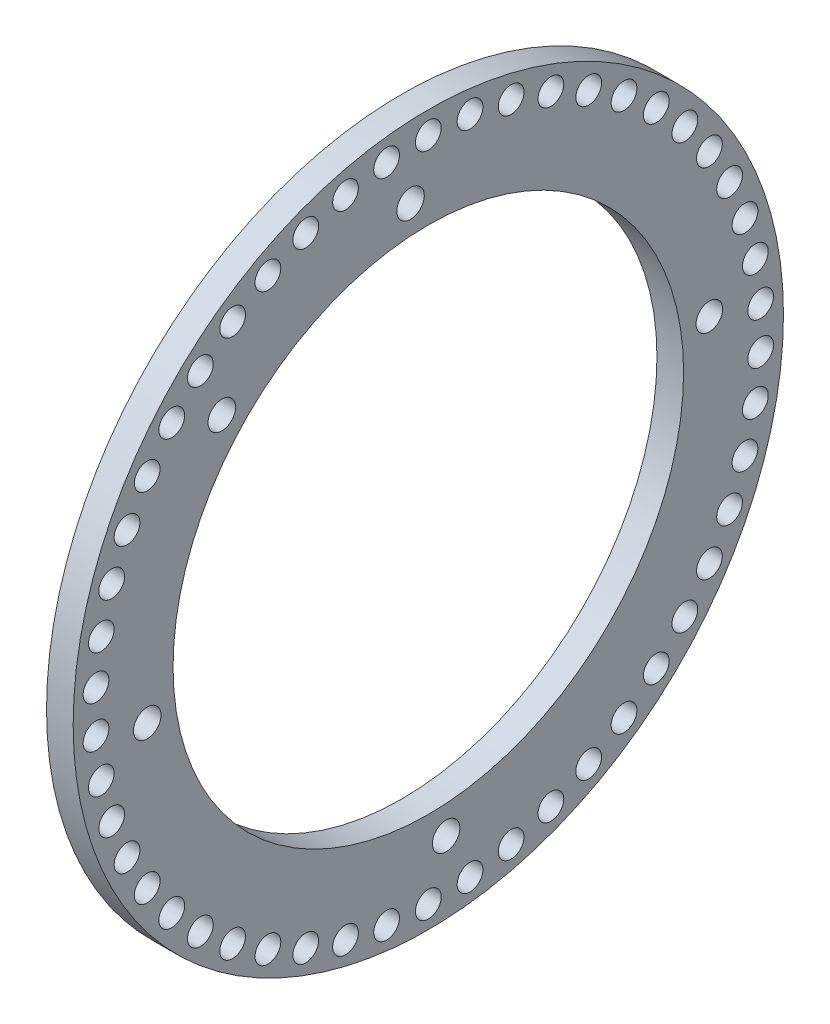
SolidWorks part; units mm, degrees
material "AISI 304"
ref_plane "Front Plane" through (0, 0, 0) normal (0, 0, 1) x (1, 0, 0)
ref_plane "Top Plane" through (0, 0, 0) normal (0, 1, 0) x (1, 0, 0)
ref_plane "Right Plane" through (0, 0, 0) normal (1, 0, 0) x (0, 0, -1)
sketch "Sketch1" plane through (0, 0, 0) normal (1, 0, 0) x (0, 0, -1)
  line L0 (0, 0) -> (0, 40) construction
  line L66 (0, 0) -> (40, 0) construction
  line L67 (0, 0) -> (-40, 0) construction
  line L72 (0, 0) -> (0, -40) construction
  circle A3 centre (0, 0) radius 40
  circle A24 centre (0, 37.5) radius 1.45
  circle A25 centre (0, 0) radius 28.75
  circle A26 centre (4.7, 37.2043) radius 1.45
  circle A27 centre (9.3259, 36.3219) radius 1.45
  circle A28 centre (13.8047, 34.8666) radius 1.45
  circle A29 centre (18.0658, 32.8615) radius 1.45
  circle A30 centre (22.0419, 30.3381) radius 1.45
  circle A31 centre (25.6705, 27.3363) radius 1.45
  circle A32 centre (28.8942, 23.9034) radius 1.45
  circle A33 centre (31.6623, 20.0935) radius 1.45
  circle A34 centre (33.931, 15.9667) radius 1.45
  circle A35 centre (35.6646, 11.5881) radius 1.45
  circle A36 centre (36.8358, 7.0268) radius 1.45
  circle A37 centre (37.426, 2.3546) radius 1.45
  circle A38 centre (37.426, -2.3546) radius 1.45
  circle A39 centre (36.8358, -7.0268) radius 1.45
  circle A40 centre (35.6646, -11.5881) radius 1.45
  circle A41 centre (33.931, -15.9667) radius 1.45
  circle A42 centre (31.6623, -20.0935) radius 1.45
  circle A43 centre (28.8942, -23.9034) radius 1.45
  circle A44 centre (25.6705, -27.3363) radius 1.45
  circle A45 centre (22.0419, -30.3381) radius 1.45
  circle A46 centre (18.0658, -32.8615) radius 1.45
  circle A47 centre (13.8047, -34.8666) radius 1.45
  circle A48 centre (9.3259, -36.3219) radius 1.45
  circle A49 centre (4.7, -37.2043) radius 1.45
  circle A50 centre (0, -37.5) radius 1.45
  circle A51 centre (-4.7, -37.2043) radius 1.45
  circle A52 centre (-9.3259, -36.3219) radius 1.45
  circle A53 centre (-13.8047, -34.8666) radius 1.45
  circle A54 centre (-18.0658, -32.8615) radius 1.45
  circle A55 centre (-22.0419, -30.3381) radius 1.45
  circle A56 centre (-25.6705, -27.3363) radius 1.45
  circle A57 centre (-28.8942, -23.9034) radius 1.45
  circle A58 centre (-31.6623, -20.0935) radius 1.45
  circle A59 centre (-33.931, -15.9667) radius 1.45
  circle A60 centre (-35.6646, -11.5881) radius 1.45
  circle A61 centre (-36.8358, -7.0268) radius 1.45
  circle A62 centre (-37.426, -2.3546) radius 1.45
  circle A63 centre (-37.426, 2.3546) radius 1.45
  circle A64 centre (-36.8358, 7.0268) radius 1.45
  circle A65 centre (-35.6646, 11.5881) radius 1.45
  circle A66 centre (-33.931, 15.9667) radius 1.45
  circle A67 centre (-31.6623, 20.0935) radius 1.45
  circle A68 centre (-28.8942, 23.9034) radius 1.45
  circle A69 centre (-25.6705, 27.3363) radius 1.45
  circle A70 centre (-22.0419, 30.3381) radius 1.45
  circle A71 centre (-18.0658, 32.8615) radius 1.45
  circle A72 centre (-13.8047, 34.8666) radius 1.45
  circle A73 centre (-9.3259, 36.3219) radius 1.45
  circle A74 centre (-4.7, 37.2043) radius 1.45
  circle A75 centre (-2.0035, 31.8444) radius 1.55
  circle A76 centre (-31.6557, -3.999) radius 1.55
  circle A77 centre (2.0035, -31.8444) radius 1.55
  circle A78 centre (31.6557, 3.999) radius 1.5
  circle A79 centre (-23.2594, 21.8421) radius 1.55
  point P9 (0, -20)
  point P11 (-20, 0)
  point P29 (20, 0)
  point P75 (0, 0)
  point P93 (0, 0)
  point P95 (0, 0)
  point P117 (0, 0)
  dimension "D1" = 50
  dimension "D2" = 80
  dimension "D3" = 57.5
  dimension "D5" = 2.5
  dimension "D10" = 6
  dimension "D4" = 2.9
  dimension "D14" = 3.1
  dimension "D15" = 3.1
  dimension "D16" = 3.1
  dimension "D17" = 3
  dimension "D18" = 3.1
  dimension "D6" = 6
  dimension "D7" = 6
  dimension "D8" = 6
  dimension "D9" = 6
  dimension "D12" = 6
  dimension "D13" = 6
  dimension "D11" = 6
  dimension "D19" = 6
  dimension "D20" = 6
extrude "Boss-Extrude4" add sketch "Sketch1" along normal blind 3
